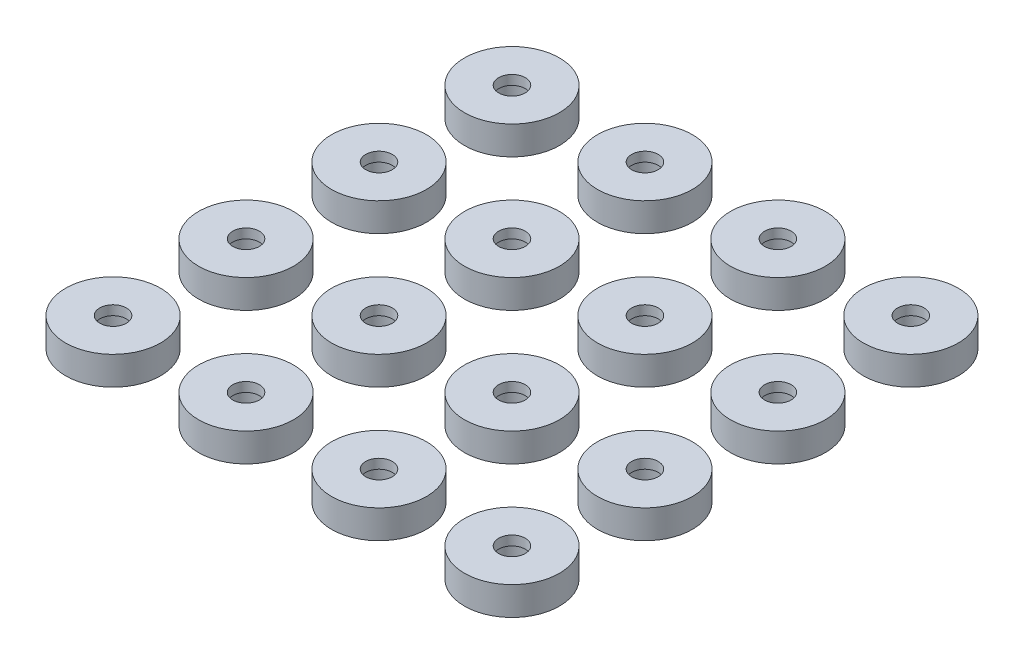
SolidWorks part; units mm, degrees
ref_plane "前视基准面" through (0, 0, 0) normal (0, 0, 1) x (1, 0, 0)
ref_plane "上视基准面" through (0, 0, 0) normal (0, 1, 0) x (1, 0, 0)
ref_plane "右视基准面" through (0, 0, 0) normal (1, 0, 0) x (0, 0, -1)
other "Configuration Table"
sketch "草图1" plane through (0, 0, 0) normal (0, 1, 0) x (1, 0, 0)
  circle A0 centre (0, 0) radius 2.5
  circle A1 centre (0, 0) radius 0.7
  circle A2 centre (0, 0) radius 1
  dimension "D1" = 1.4
  dimension "D2" = 2
  dimension "D3" = 5
extrude "凸台-拉伸1" add sketch "草图1" along normal blind 1.5 contours A0
extrude "切除-拉伸2" cut sketch "草图1<5>" along normal blind 1 contours A2
sketch "草图1<5>" plane through (0, 0, 0) normal (0, 1, 0) x (1, 0, 0) same geometry as "草图1"
extrude "切除-拉伸3" cut sketch "草图1<6>" along normal through all contours A1 region at (0, 0, 0)
sketch "草图1<6>" plane through (0, 0, 0) normal (0, 1, 0) x (1, 0, 0) same geometry as "草图1"
ref_plane "基准面1" through (0, 0, 3) normal (0, 0, 1) x (1, 0, 0)
pattern_linear "阵列(线性)1" count 4 spacing 7 along (0, 0, 1) of bodies 108
ref_plane "基准面2" through (3, 0, 0) normal (1, 0, 0) x (0, 0, -1)
pattern_linear "阵列(线性)2" count 4 spacing 7 along (1, 0, 0) of bodies 117 108 109 110
